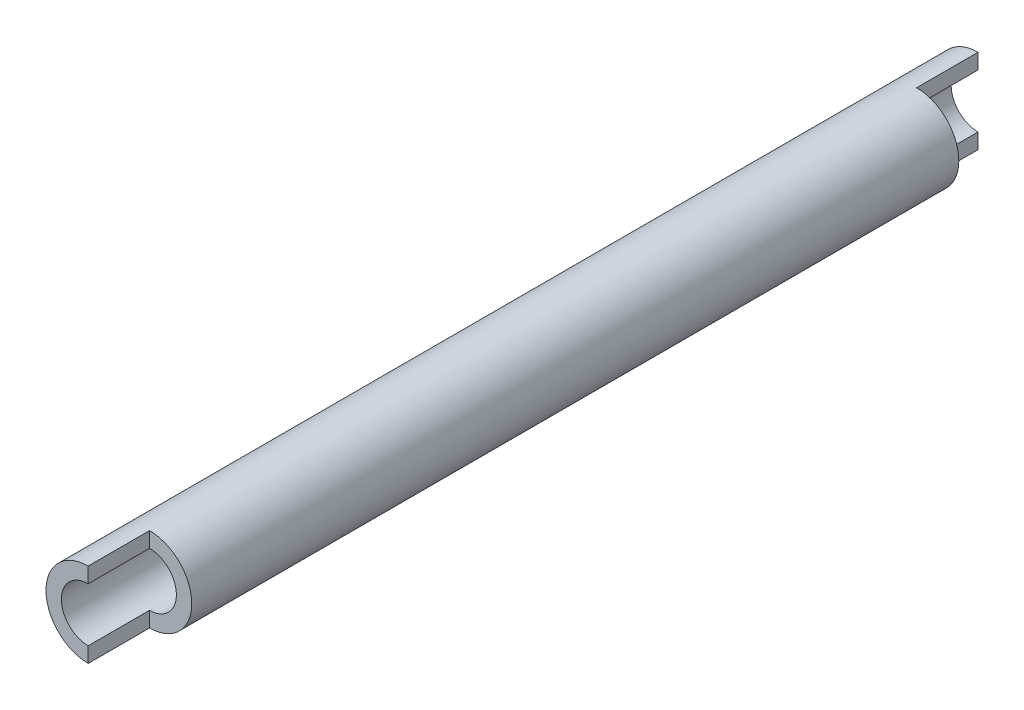
SolidWorks part; units mm, degrees
ref_plane "Płaszczyzna przednia" through (0, 0, 0) normal (0, 0, 1) x (1, 0, 0)
ref_plane "Płaszczyzna górna" through (0, 0, 0) normal (0, 1, 0) x (1, 0, 0)
ref_plane "Płaszczyzna prawa" through (0, 0, 0) normal (1, 0, 0) x (0, 0, -1)
sketch "Sketch1" plane through (0, 0, 0) normal (0, 0, 1) x (1, 0, 0)
  line L0 (-5.5, 0) -> (0, 0) construction
  line L1 (0, 0) -> (0, -5.5) construction
  circle A1 centre (0, 0) radius 3.5
  circle A2 centre (0, 0) radius 5.5
  dimension "D1" = 7
  dimension "D2" = 11
extrude "Boss-Extrude1 dlugosc calkowita" add sketch "Sketch1" along normal blind 100
sketch "Sketch2" plane through (0, 0, 0) normal (0, 0, -1) x (-1, 0, 0)
  line L0 (0, 5.5) -> (0, 3.5)
  line L1 (0, -3.5) -> (0, -5.5)
  arc A0 (0, -5.5) -> (0, 5.5) centre (0, 0) ccw
  arc A1 (0, -3.5) -> (0, 3.5) centre (0, 0) ccw
  circle A2 centre (0, 0) radius 5.5 construction
  dimension "D1" = 5.5
  dimension "D2" = 3.5
extrude "Boss-Extrude2 przedluzenie do montazu" add sketch "Sketch2" along normal blind 8 and the other way offset from surface (108 mm away) 8 other way up to face at (5.5, 0, 100)
equation "\"D1@Boss-Extrude1 dlugosc calkowita\" = \"dlugosc S3\""
equation "\"dlugosc S3\"= 100"
equation "\"dlugosc S4\"= 150"
equation "\"dlugosc S1\"= 1"
equation "\"dlugosc S2\"= 50"
